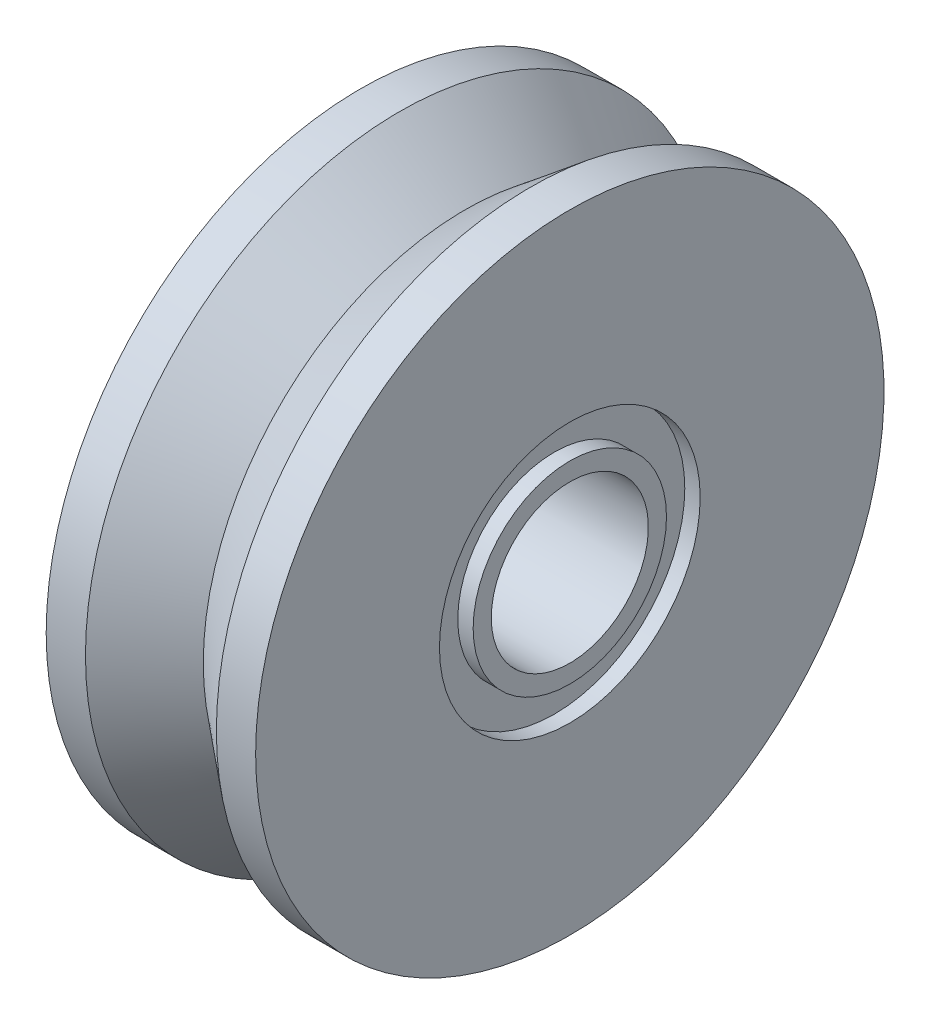
SolidWorks part; units mm, degrees
ref_plane "Front Plane" through (0, 0, 0) normal (0, 0, 1) x (1, 0, 0)
ref_plane "Top Plane" through (0, 0, 0) normal (0, 1, 0) x (1, 0, 0)
ref_plane "Right Plane" through (0, 0, 0) normal (1, 0, 0) x (0, 0, -1)
sketch "Sketch1" plane through (0, 0, 0) normal (0, 0, 1) x (1, 0, 0)
  line L0 (0, 0) -> (0, 1.5) construction
  line L1 (0, 6) -> (0.75, 6)
  line L2 (0, 1.5) -> (4, 1.5)
  line L3 (0, 1.5) -> (0, 1.8462)
  line L4 (0.75, 6) -> (2, 5)
  line L5 (4, 2.4895) -> (4, 6)
  line L6 (2, 5) -> (3.25, 6)
  line L7 (3.25, 6) -> (4, 6)
  line L8 (0, 0) -> (13.2867, 0) construction
  line L9 (0, 2.4895) -> (0, 6)
  line L10 (0, 1.8462) -> (0.2937, 1.8462)
  line L11 (4, 1.8462) -> (4, 1.5)
  line L12 (0, 2.4895) -> (0.2937, 2.4895)
  line L13 (0.2937, 1.8462) -> (0.2937, 2.4895)
  line L14 (4, 1.8462) -> (3.7063, 1.8462)
  line L16 (4, 2.4895) -> (3.7063, 2.4895)
  line L17 (3.7063, 1.8462) -> (3.7063, 2.4895)
  dimension "D1" = 4
  dimension "D2" = 1.5
  dimension "D3" = 6
  dimension "D4" = 2.5
  dimension "D5" = 1
  dimension "D6" = 0.3462
  dimension "D7" = 0.2937
revolve "Revolve1" add sketch "Sketch1" angle 360 about L8
ref_plane "Plane1" through (0, 0, 5.25) normal (0, 0, 1) x (1, 0, 0)
ref_plane "Plane2" through (2, 0, 0) normal (1, 0, 0) x (0, 0, -1)
